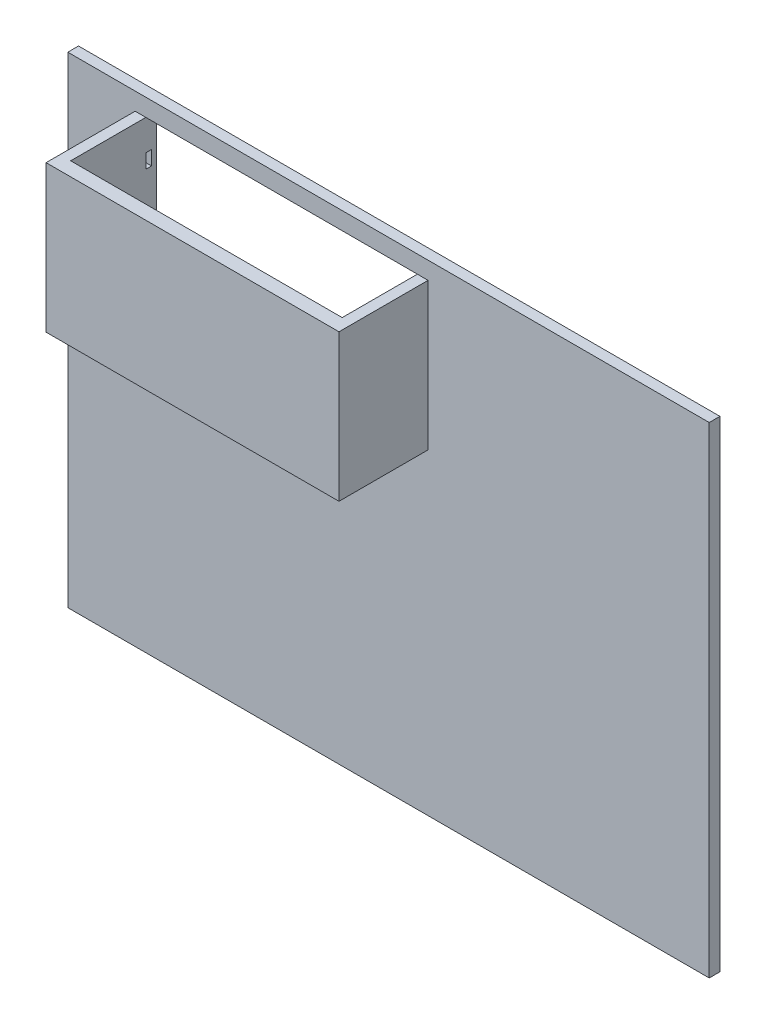
SolidWorks part; units mm, degrees
ref_plane "前视基准面" through (0, 0, 0) normal (0, 0, 1) x (1, 0, 0)
ref_plane "上视基准面" through (0, 0, 0) normal (0, 1, 0) x (1, 0, 0)
ref_plane "右视基准面" through (0, 0, 0) normal (1, 0, 0) x (0, 0, -1)
sketch "草图1" plane through (0, 0, 0) normal (0, 0, 1) x (1, 0, 0)
  line L1 (-90, 67.5) -> (90, 67.5)
  line L2 (-90, 67.5) -> (-90, -67.5)
  line L3 (-90, -67.5) -> (90, -67.5)
  line L4 (90, 67.5) -> (90, -67.5)
  line L5 (-90, 67.5) -> (90, -67.5) construction
  line L6 (-90, -67.5) -> (90, 67.5) construction
  point P0 (0, 0)
  dimension "D1" = 135
  dimension "D2" = 180
extrude "凸台-拉伸1" add sketch "草图1" along normal blind 3
sketch "草图7" plane through (0, 0, 0) normal (0, 0, -1) x (-1, 0, 0)
  line L0 (-90, 67.5) -> (90, 67.5) construction
  line L1 (-8.1, 62.6) -> (68.1, 62.6)
  line L2 (-8.1, 62.6) -> (-8.1, 21.4)
  line L3 (-8.1, 21.4) -> (68.1, 21.4)
  line L4 (68.1, 62.6) -> (68.1, 21.4)
  line L5 (90, 67.5) -> (90, -67.5) construction
  dimension "D1" = 41.2
  dimension "D2" = 76.2
  dimension "D3" = 4.9
  dimension "D4" = 21.9
extrude "切除-拉伸3" cut sketch "草图7" against normal up to next
sketch "草图4" plane through (0, 0, 0) normal (0, 0, -1) x (-1, 0, 0)
  line L0 (68.1, 21.4) -> (68.1, 62.6) construction
  line L5 (68.1, 42) -> (94.8483, 42) construction
  line L10 (83.2374, -53.4277) -> (79.3374, -53.4277) construction
  line L11 (83.2374, -49.6277) -> (83.2374, -53.4277) construction
  line L12 (79.3374, -49.6277) -> (83.2374, -49.6277) construction
  line L13 (68.1, 30) -> (68.1, 34)
  line L20 (72.1, 30) -> (68.1, 30)
  line L21 (72.1, 34) -> (72.1, 30)
  line L22 (68.1, 34) -> (72.1, 34)
  line L29 (68.1, 50) -> (72.1, 50)
  line L30 (72.1, 50) -> (72.1, 54)
  line L31 (72.1, 54) -> (68.1, 54)
  line L32 (68.1, 54) -> (68.1, 50)
  point P6 (70.1, 50)
  point P8 (25.1715, -14.7221)
  dimension "D1" = 4
  dimension "D2" = 4
  dimension "D3" = 8
extrude "切除-拉伸2" cut sketch "草图4" along normal blind 1.6 from surface starting at face at (-30, 42, 3)
sketch "草图8" plane through (0, 0, 3) normal (0, 0, 1) x (1, 0, 0)
  line L0 (-68.1, 21.4) -> (-68.1, 30) construction
  line L1 (11.1, 21.4) -> (8.1, 21.4)
  line L2 (11.1, 21.4) -> (11.1, 62.6)
  line L3 (11.1, 62.6) -> (8.1, 62.6)
  line L4 (8.1, 21.4) -> (8.1, 62.6)
  line L5 (-68.1, 21.4) -> (-71.1, 21.4)
  line L6 (-68.1, 21.4) -> (-68.1, 62.6)
  line L7 (-68.1, 62.6) -> (-71.1, 62.6)
  line L8 (-71.1, 21.4) -> (-71.1, 62.6)
  line L9 (-68.1, 62.6) -> (8.1, 62.6) construction
  line L10 (8.1, 21.4) -> (-68.1, 21.4) construction
  line L11 (8.1, 62.6) -> (8.1, 21.4) construction
  dimension "D1" = 3
extrude "凸台-拉伸2" add sketch "草图8" along normal blind 25
sketch "草图9" plane through (0, 0, 28) normal (0, 0, 1) x (1, 0, 0)
  line L1 (11.1, 21.4) -> (-71.1, 21.4)
  line L2 (11.1, 21.4) -> (11.1, 62.6)
  line L3 (11.1, 62.6) -> (-71.1, 62.6)
  line L4 (-71.1, 21.4) -> (-71.1, 62.6)
extrude "凸台-拉伸3" add sketch "草图9" against normal blind 3.9
